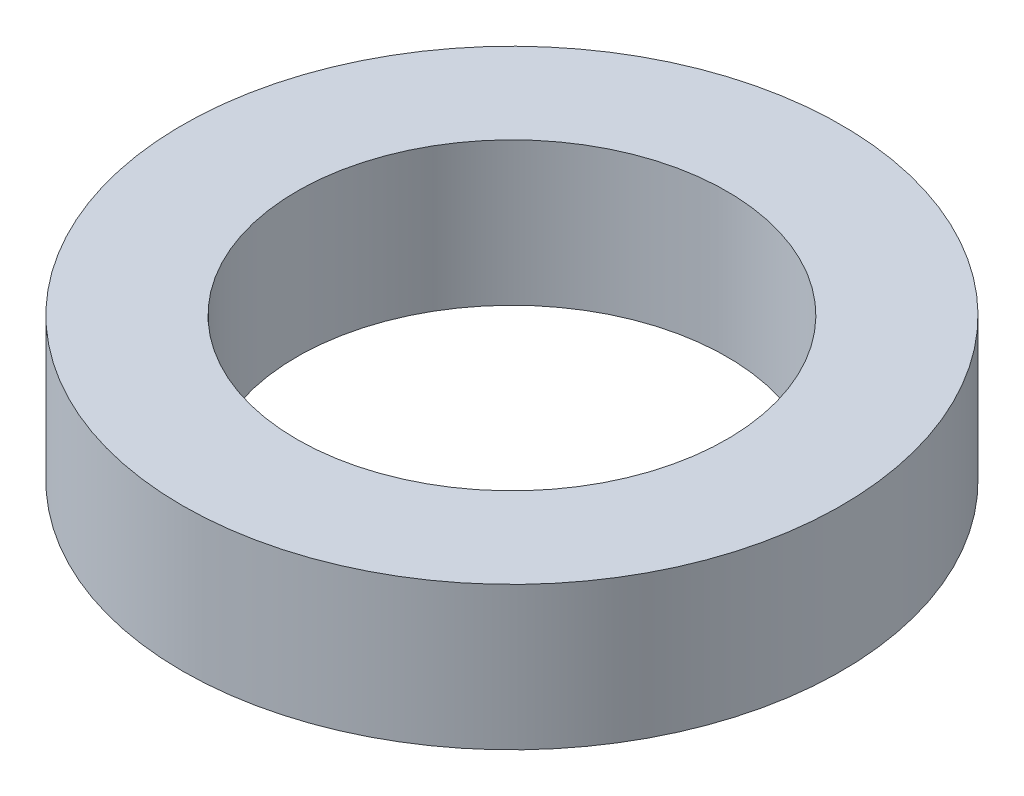
SolidWorks part; units mm, degrees
ref_plane "Front Plane" through (0, 0, 0) normal (0, 0, 1) x (1, 0, 0)
ref_plane "Top Plane" through (0, 0, 0) normal (0, 1, 0) x (1, 0, 0)
ref_plane "Right Plane" through (0, 0, 0) normal (1, 0, 0) x (0, 0, -1)
sketch "Sketch1" plane through (0, 0, 0) normal (0, 1, 0) x (1, 0, 0)
  circle A0 centre (0, 0) radius 57.5
  dimension "FLANGE_OD" = 115
extrude "Boss-Extrude1" add sketch "Sketch1" along normal blind 25
sketch "Sketch2" plane through (0, 0, 0) normal (0, 1, 0) x (1, 0, 0)
  circle A0 centre (0, 0) radius 37.5
  dimension "BORE_D" = 75
extrude "Cut-Extrude1" cut sketch "Sketch2" along normal through all
sketch "Sketch3" plane through (0, 25, 0) normal (0, 1, 0) x (1, 0, 0)
  circle A0 centre (0, 0) radius 21.7414 construction
  circle A1 centre (-21.7414, 0) radius 1.9779
  dimension "BOLT_D" = 3.9557
  dimension "BOLT_PCD" = 43.4829
extrude "Cut-Extrude2" cut sketch "Sketch3" against normal blind 21.3773 rebuild error yes
pattern_circular "CirPattern1" count 8 over 360 rebuild error yes
